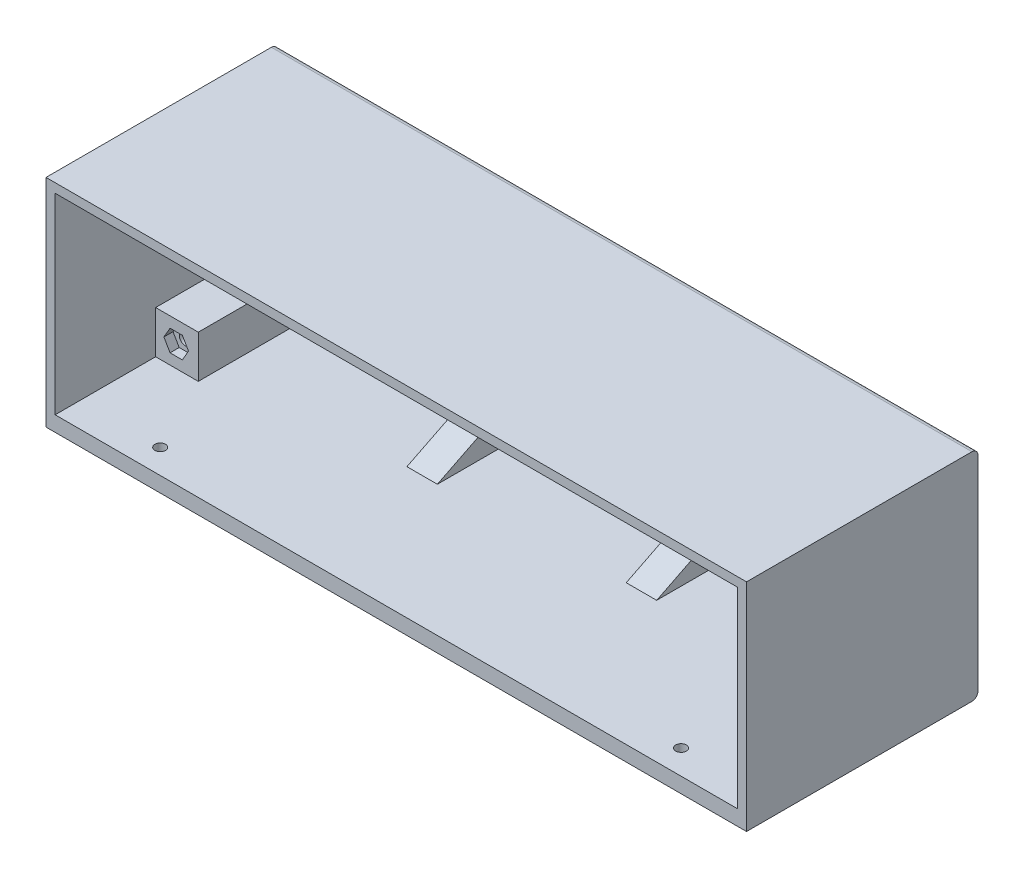
SolidWorks part; units mm, degrees
note: The reader was unsure of these and kept them because the rebuilt part matched: shared geometry of "草图1<3>", "草图12<2>".
ref_plane "前视基准面" through (0, 0, 0) normal (0, 0, 1) x (1, 0, 0)
ref_plane "上视基准面" through (0, 0, 0) normal (0, 1, 0) x (1, 0, 0)
ref_plane "右视基准面" through (0, 0, 0) normal (1, 0, 0) x (0, 0, -1)
sketch "草图1" plane through (0, 0, 0) normal (0, 0, 1) x (1, 0, 0)
  line L1 (-112, -31.5) -> (112, -31.5)
  line L2 (-112, -31.5) -> (-112, 31.5)
  line L3 (-112, 31.5) -> (112, 31.5)
  line L4 (112, -31.5) -> (112, 31.5)
  line L5 (-112, -31.5) -> (112, 31.5) construction
  line L6 (-112, 31.5) -> (112, -31.5) construction
  point P1 (0, 0)
  dimension "D1" = 224
  dimension "D2" = 63
extrude "凸台-拉伸6" add sketch "草图1" along normal blind 3
extrude "拉伸-薄壁1" add sketch "草图1<3>" along normal blind 76 thin thin type one direction wall 3
sketch "草图1<3>" plane through (0, 0, 0) normal (0, 0, 1) x (1, 0, 0) same geometry as "草图1"
sketch "草图6" plane through (0, 0, 0) normal (0, 0, -1) x (-1, 0, 0)
  line L0 (-95.55, -23.5) -> (-72.05, -23.5)
  line L1 (-95.55, -23.5) -> (-95.55, 11.5)
  line L2 (-95.55, 11.5) -> (-72.05, 11.5)
  line L3 (-72.05, -23.5) -> (-72.05, 11.5)
  line L4 (-95.55, -23.5) -> (-72.05, 11.5) construction
  line L5 (-95.55, 11.5) -> (-72.05, -23.5) construction
  line L6 (-67.55, -24.5) -> (-67.55, 10.5)
  line L7 (-67.55, 10.5) -> (-43.55, 10.5)
  line L8 (-43.55, -24.5) -> (-43.55, 10.5)
  line L9 (-67.55, -24.5) -> (-43.55, -24.5)
  line L10 (-26.25, -24.5) -> (-26.25, 10.5)
  line L11 (-26.25, 10.5) -> (-2.25, 10.5)
  line L12 (-2.25, -24.5) -> (-2.25, 10.5)
  line L13 (-26.25, -24.5) -> (-2.25, -24.5)
  line L14 (2.25, -24.5) -> (2.25, 10.5)
  line L15 (2.25, 10.5) -> (26.25, 10.5)
  line L16 (26.25, -24.5) -> (26.25, 10.5)
  line L17 (2.25, -24.5) -> (26.25, -24.5)
  line L18 (43.55, -24.5) -> (43.55, 10.5)
  line L19 (43.55, 10.5) -> (67.55, 10.5)
  line L20 (67.55, -24.5) -> (67.55, 10.5)
  line L21 (43.55, -24.5) -> (67.55, -24.5)
  line L22 (72.05, -24.5) -> (72.05, 10.5)
  line L23 (72.05, 10.5) -> (95.55, 10.5)
  line L24 (95.55, -24.5) -> (95.55, 10.5)
  line L25 (72.05, -24.5) -> (95.55, -24.5)
  line L28 (-112, -31.5) -> (-112, 31.5) construction
  line L29 (112, -31.5) -> (112, 31.5) construction
  line L31 (112, -31.5) -> (-112, -31.5) construction
  point P0 (-83.8, -6)
  dimension "D1" = 35
  dimension "D2" = 16.45
  dimension "D3" = 4.5
  dimension "D4" = 17.3
  dimension "D5" = 4.5
  dimension "D6" = 17.3
  dimension "D7" = 4.5
  dimension "D8" = 16.45
  dimension "D9" = 8
extrude "切除-拉伸1" cut sketch "草图6" against normal blind 4
sketch "草图8" plane through (0, 0, 3) normal (0, 0, 1) x (1, 0, 0)
  line L1 (-112, 31.5) -> (-98, 31.5)
  line L2 (-112, 31.5) -> (-112, 17.5)
  line L3 (-112, 17.5) -> (-98, 17.5)
  line L4 (-98, 31.5) -> (-98, 17.5)
  line L16 (-112, -17.5) -> (-98, -17.5)
  line L17 (-112, -17.5) -> (-112, -31.5)
  line L18 (-112, -31.5) -> (-98, -31.5)
  line L19 (-98, -17.5) -> (-98, -31.5)
  dimension "D1" = 14
  dimension "D2" = 14
  dimension "D5" = 14
  dimension "D6" = 14
extrude "凸台-拉伸8" add sketch "草图8" along normal blind 40
sketch "草图11" plane through (0, 0, 43) normal (0, 0, 1) x (1, 0, 0)
  line L2 (-112, 31.5) -> (-112, 17.5) construction
  line L3 (-98, 31.5) -> (-112, 31.5) construction
  line L6 (-112, -17.5) -> (-112, -31.5) construction
  line L8 (-112, -31.5) -> (-98, -31.5) construction
  circle A0 centre (-105.25, 24.51) radius 2
  circle A4 centre (-105.25, -24.51) radius 2
  dimension "D1" = 4
  dimension "D2" = 6.99
  dimension "D3" = 6.75
  dimension "D8" = 6.75
  dimension "D9" = 6.99
extrude "切除-拉伸2" cut sketch "草图11" against normal blind 10
sketch "草图12" plane through (0, 0, 43) normal (0, 0, 1) x (1, 0, 0)
  line L1 (-107.2707, 28.01) -> (-109.2915, 24.51)
  line L2 (-109.2915, 24.51) -> (-107.2707, 21.01)
  line L3 (-107.2707, 21.01) -> (-103.2293, 21.01)
  line L4 (-103.2293, 21.01) -> (-101.2085, 24.51)
  line L5 (-101.2085, 24.51) -> (-103.2293, 28.01)
  line L6 (-103.2293, 28.01) -> (-107.2707, 28.01)
  line L7 (-101.2085, -24.51) -> (-103.2293, -21.01)
  line L8 (-103.2293, -21.01) -> (-107.2707, -21.01)
  line L9 (-107.2707, -21.01) -> (-109.2915, -24.51)
  line L10 (-109.2915, -24.51) -> (-107.2707, -28.01)
  line L11 (-107.2707, -28.01) -> (-103.2293, -28.01)
  line L12 (-103.2293, -28.01) -> (-101.2085, -24.51)
  circle A0 centre (-105.25, 24.51) radius 3.5 construction
  circle A1 centre (-105.25, -24.51) radius 3.5 construction
  point P10 (-102.2189, 22.76)
  dimension "D1" = 3.5
  dimension "D2" = 3.5
extrude "切除-拉伸4" cut sketch "草图12<2>" against normal blind 3
sketch "草图12<2>" plane through (0, 0, 43) normal (0, 0, 1) x (1, 0, 0) same geometry as "草图12"
sketch "草图14" plane through (0, 0, 0) normal (0, 0, -1) x (-1, 0, 0)
  line L1 (-112, 31.5) -> (-98, 31.5)
  line L2 (-112, 31.5) -> (-112, 17.5)
  line L3 (-112, 17.5) -> (-98, 17.5)
  line L4 (-98, 31.5) -> (-98, 17.5)
  line L5 (-112, -31.5) -> (-98, -31.5)
  line L6 (-112, -31.5) -> (-112, -17.5)
  line L7 (-112, -17.5) -> (-98, -17.5)
  line L8 (-98, -31.5) -> (-98, -17.5)
  dimension "D1" = 14
  dimension "D2" = 14
  dimension "D3" = 14
  dimension "D4" = 14
extrude "凸台-拉伸9" add sketch "草图14" against normal blind 44.5
sketch "草图15" plane through (0, 0, 44.5) normal (0, 0, 1) x (1, 0, 0)
  line L0 (112, 31.5) -> (112, 17.5) construction
  line L7 (98, 31.5) -> (112, 31.5) construction
  line L8 (112, -17.5) -> (112, -31.5) construction
  line L10 (112, -31.5) -> (98, -31.5) construction
  circle A0 centre (105.25, 24.5145) radius 2
  circle A1 centre (105.25, -24.51) radius 2
  point P11 (105, 31.5)
  dimension "D2" = 4
  dimension "D3" = 6.99
  dimension "D1" = 6.75
  dimension "D4" = 6.75
  dimension "D5" = 6.99
extrude "切除-拉伸5" cut sketch "草图15" against normal blind 13
sketch "草图16" plane through (0, 0, 44.5) normal (0, 0, 1) x (1, 0, 0)
  line L1 (103.2293, 21.0145) -> (107.2707, 21.0145)
  line L2 (107.2707, 21.0145) -> (109.2915, 24.5145)
  line L3 (109.2915, 24.5145) -> (107.2707, 28.0145)
  line L4 (107.2707, 28.0145) -> (103.2293, 28.0145)
  line L5 (103.2293, 28.0145) -> (101.2085, 24.5145)
  line L6 (101.2085, 24.5145) -> (103.2293, 21.0145)
  line L7 (103.2293, -28.01) -> (107.2707, -28.01)
  line L8 (107.2707, -28.01) -> (109.2915, -24.51)
  line L9 (109.2915, -24.51) -> (107.2707, -21.01)
  line L10 (107.2707, -21.01) -> (103.2293, -21.01)
  line L11 (103.2293, -21.01) -> (101.2085, -24.51)
  line L12 (101.2085, -24.51) -> (103.2293, -28.01)
  circle A0 centre (105.25, 24.5145) radius 3.5 construction
  circle A1 centre (105.25, -24.51) radius 3.5 construction
  dimension "D1" = 3.5
  dimension "D2" = 3.5
extrude "切除-拉伸11" cut sketch "草图16" against normal blind 6
sketch3d "3D草图1" plane through (0, 0, 0) normal (0, 0, 1) x (1, 0, 0)
  dimension "D1" = 80.5
  dimension "D2" = 80.5
sketch "草图21" plane through (-34.5, 0, 0) normal (-1, 0, 0) x (0, 0, 1)
  line L0 (3, 31.5) -> (33, 31.5)
  line L1 (33, 31.5) -> (3, 16.5)
  line L2 (3, 16.5) -> (3, 31.5)
  line L3 (43, 31.5) -> (3, 31.5) construction
  line L4 (3, 17.5) -> (3, 31.5) construction
  line L5 (3, -16.5) -> (3, -31.5)
  line L6 (3, -31.5) -> (33, -31.5)
  line L7 (33, -31.5) -> (3, -16.5)
  line L8 (3, -31.5) -> (3, -17.5) construction
  line L9 (43, -31.5) -> (3, -31.5) construction
  dimension "D1" = 30
  dimension "D2" = 15
sketch "草图22" plane through (34.5, 0, 0) normal (1, 0, 0) x (0, 0, -1)
  line L0 (-3, 31.5) -> (-3, 16.5)
  line L1 (-3, 16.5) -> (-33, 31.5)
  line L2 (-33, 31.5) -> (-3, 31.5)
  line L3 (-3, 31.5) -> (-33, 31.5) construction
  line L4 (-3, 16.5) -> (-3, 31.5) construction
  line L5 (0, -16.5) -> (0, -31.5)
  line L6 (0, -31.5) -> (-30, -31.5)
  line L7 (-30, -31.5) -> (0, -16.5)
  line L8 (-3, -31.5) -> (-3, -17.5) construction
  line L9 (-43, -31.5) -> (-3, -31.5) construction
extrude "凸台-拉伸10" add sketch "草图21" along normal mid plane 10
extrude "凸台-拉伸11" add sketch "草图22" along normal mid plane 10
sketch "草图30" plane through (0, 0, 0) normal (0, 0, -1) x (-1, 0, 0)
  line L1 (-115, -34.5) -> (115, -34.5)
  line L2 (-115, -34.5) -> (-115, -36.5)
  line L3 (-115, -36.5) -> (115, -36.5)
  line L4 (115, -34.5) -> (115, -36.5)
  dimension "D1" = 2
  dimension "D2" = 230
extrude "凸台-拉伸13" add sketch "草图30" against normal blind 76
fillet "圆角3" radius 2 2 edges at (0, 34.5, 0) (0, -36.5, 0)
sketch "草图28" plane through (0, -31.5, 0) normal (0, 1, 0) x (1, 0, 0)
  circle A2 centre (85.5, -68) radius 1.75
  circle A3 centre (-85.5, -68) radius 1.75
  dimension "D1" = 3.5
  dimension "D2" = 3.5
sketch "草图31" plane through (0, -36.5, 0) normal (0, -1, 0) x (1, 0, 0)
  line L0 (115, 76) -> (-115, 76) construction
  line L3 (-115, 76) -> (-115, 2) construction
  line L4 (115, 76) -> (115, 2) construction
  circle A0 centre (-85.5, 68) radius 2.75
  circle A1 centre (85.5, 68) radius 2.75
  dimension "D1" = 5.5
  dimension "D2" = 5.5
  dimension "D3" = 8
  dimension "D4" = 29.5
  dimension "D5" = 8
  dimension "D6" = 29.5
extrude "切除-拉伸13" cut sketch "草图31" against normal blind 2.5
extrude "切除-拉伸14" cut sketch "草图28" against normal blind 2.5
extrude "切除-拉伸3" cut sketch "草图12" against normal blind 3
sketch "草图13" plane through (0, 0, 0) normal (0, 0, -1) x (-1, 0, 0)
  line L1 (-84.9613, 53.4178) -> (-70.9613, 53.4178)
  line L2 (-84.9613, 53.4178) -> (-84.9613, 39.4178)
  line L3 (-84.9613, 39.4178) -> (-70.9613, 39.4178)
  line L4 (-70.9613, 53.4178) -> (-70.9613, 39.4178)
  line L12 (-84.9613, 2.4178) -> (-70.9613, 2.4178)
  line L13 (-84.9613, 2.4178) -> (-84.9613, -11.5822)
  line L14 (-84.9613, -11.5822) -> (-70.9613, -11.5822)
  line L15 (-70.9613, 2.4178) -> (-70.9613, -11.5822)
